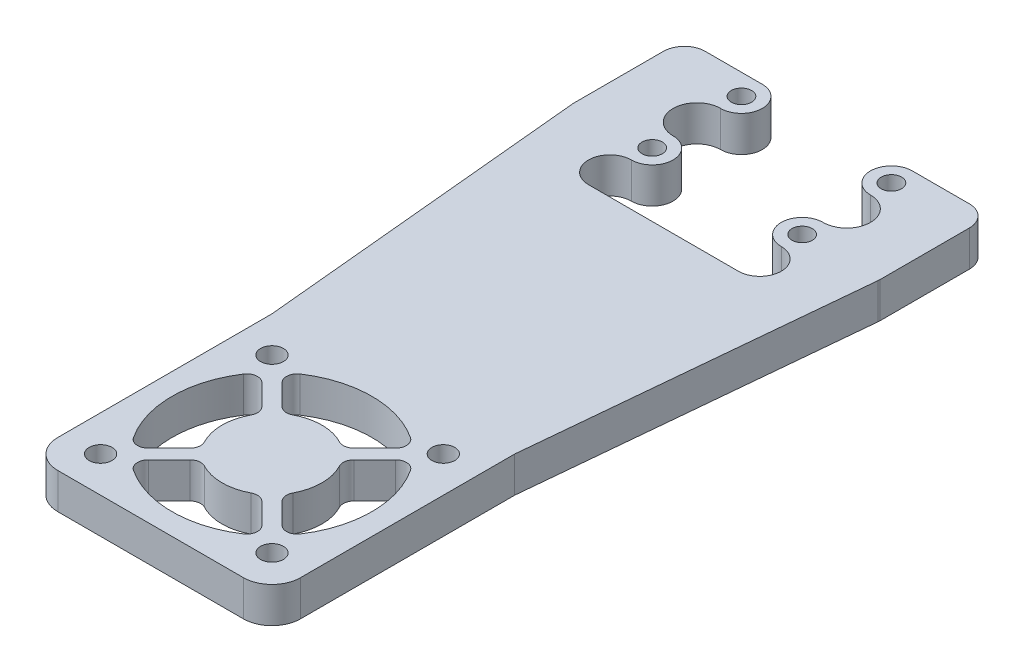
SolidWorks part; units mm, degrees
ref_plane "Front Plane" through (0, 0, 0) normal (0, 0, 1) x (1, 0, 0)
ref_plane "Top Plane" through (0, 0, 0) normal (0, 1, 0) x (1, 0, 0)
ref_plane "Right Plane" through (0, 0, 0) normal (1, 0, 0) x (0, 0, -1)
sketch "Sketch1" plane through (0, 0, 0) normal (0, 1, 0) x (1, 0, 0)
  line L0 (0, 0) -> (0, 70) construction
  line L1 (-12, -12) -> (12, -12) construction
  line L2 (-12, -12) -> (-12, 12) construction
  line L3 (-12, 12) -> (12, 12) construction
  line L4 (12, -12) -> (12, 12) construction
  line L5 (-12, -12) -> (12, 12) construction
  line L6 (-12, 12) -> (12, -12) construction
  line L7 (-17, -17) -> (17, -17)
  line L8 (-17, -17) -> (-17, 17)
  line L9 (-17, 17) -> (17, 17)
  line L10 (17, -17) -> (17, 17)
  line L11 (-17, -17) -> (17, 17) construction
  line L12 (-17, 17) -> (17, -17) construction
  line L13 (10.5, 63.75) -> (18.5, 63.75) construction
  line L14 (-10.5, 76.25) -> (10.5, 76.25) construction
  line L15 (-10.5, 76.25) -> (-10.5, 63.75) construction
  line L16 (-10.5, 63.75) -> (10.5, 63.75) construction
  line L17 (10.5, 76.25) -> (10.5, 63.75) construction
  line L18 (-10.5, 76.25) -> (10.5, 63.75) construction
  line L19 (-10.5, 63.75) -> (10.5, 76.25) construction
  line L20 (10.5, 66.675) -> (18.5, 66.675)
  line L21 (10.5, 60.825) -> (18.5, 60.825)
  line L22 (10.5, 76.25) -> (18.5, 76.25) construction
  line L23 (10.5, 79.175) -> (18.5, 79.175)
  line L24 (10.5, 73.325) -> (18.5, 73.325)
  line L25 (-10.5, 76.25) -> (-18.5, 76.25) construction
  line L26 (-10.5, 73.325) -> (-18.5, 73.325)
  line L27 (-10.5, 79.175) -> (-18.5, 79.175)
  line L28 (-10.5, 63.75) -> (-18.5, 63.75) construction
  line L29 (-10.5, 60.825) -> (-18.5, 60.825)
  line L30 (-10.5, 66.675) -> (-18.5, 66.675)
  line L31 (-17, 17) -> (-17, 60.825)
  line L32 (17, 17) -> (17, 60.825)
  line L33 (-10.5, 54.825) -> (10.5, 54.825)
  line L34 (-21.425, 76.25) -> (-21.425, 63.75)
  line L35 (17, 17) -> (21.4119, 63.4736)
  line L36 (-21.4119, 63.4736) -> (-17, 17)
  line L37 (21.425, 63.75) -> (21.425, 76.25)
  circle A0 centre (-12, 12) radius 1.6
  circle A1 centre (12, 12) radius 1.6
  circle A2 centre (-12, -12) radius 1.6
  circle A3 centre (12, -12) radius 1.6
  circle A4 centre (-10.5, 76.25) radius 1.425
  circle A5 centre (10.5, 76.25) radius 1.425
  circle A6 centre (10.5, 63.75) radius 1.425
  circle A7 centre (-10.5, 63.75) radius 1.425
  arc A8 (10.5, 66.675) -> (10.5, 60.825) centre (10.5, 63.75) ccw
  arc A9 (18.5, 60.825) -> (18.5, 66.675) centre (18.5, 63.75) ccw
  arc A10 (10.5, 79.175) -> (10.5, 73.325) centre (10.5, 76.25) ccw
  arc A11 (18.5, 73.325) -> (18.5, 79.175) centre (18.5, 76.25) ccw
  arc A12 (-10.5, 73.325) -> (-10.5, 79.175) centre (-10.5, 76.25) ccw
  arc A13 (-18.5, 79.175) -> (-18.5, 73.325) centre (-18.5, 76.25) ccw
  arc A14 (-10.5, 60.825) -> (-10.5, 66.675) centre (-10.5, 63.75) ccw
  arc A15 (-18.5, 66.675) -> (-18.5, 60.825) centre (-18.5, 63.75) ccw
  arc A16 (10.5, 60.825) -> (10.5, 54.825) centre (10.5, 57.825) cw
  arc A17 (-10.5, 60.825) -> (-10.5, 54.825) centre (-10.5, 57.825) ccw
  arc A18 (-10.5, 73.325) -> (-10.5, 66.675) centre (-10.5, 70) ccw
  arc A19 (10.5, 66.675) -> (10.5, 73.325) centre (10.5, 70) ccw
  point P0 (0, 0)
  point P10 (0, 0)
  point P25 (14.5, 63.75)
  point P31 (14.5, 76.25)
  point P37 (-14.5, 76.25)
  point P43 (-14.5, 63.75)
  point P65 (22.925, 68.75)
  point P66 (0, 0)
  dimension "D2" = 3.2
  dimension "D7" = 2.85
  dimension "D8" = 2.85
  dimension "D9" = 1.5
  dimension "D11" = 3
  dimension "D1" = 24
  dimension "D3" = 5
  dimension "D4" = 21
  dimension "D5" = 12.5
  dimension "D6" = 70
  dimension "D10" = 8
extrude "Boss-Extrude1" add sketch "Sketch1" along normal blind 5 contours L7 L10 L9 L8 A3 A2 A1 A0 | A17 L29 L31 L9 L32 L21 A16 L33 | A15 L36 L31 L29 | A9 L21 L32 L35 | L21 A9 L20 A8 A6 | A19 L20 A9 L37 A11 L24 | L24 A11 L23 A10 A5 | L27 A13 L26 A12 A4 | A18 L26 A13 L34 A15 L30 | L30 A15 L29 A14 A7 region at (0, 0, 0) region at (0, 0, -36.7282) region at (-18.4223, 0, -46.4573) region at (18.4223, 0, -46.4573) region at (-14.8792, 0, -63.75) region at (14.8792, 0, -63.75) region at (-17.4554, 0, -70) region at (17.4554, 0, -70) region at (-14.8792, 0, -76.25) region at (14.8792, 0, -76.25)
fillet "Fillet1" radius 4 2 edges at (17, 2.5, 17) (-17, 2.5, 17)
sketch "Sketch2" plane through (0, 5, 0) normal (0, 1, 0) x (1, 0, 0)
  line L0 (-12, 12) -> (0, 0) construction
  line L1 (-9.1671, 10.5813) -> (-4.1919, 5.6061)
  line L2 (4.1919, 5.6061) -> (9.1671, 10.5813)
  line L3 (0, 0) -> (12, 12) construction
  line L4 (-6.6795, 8.0937) -> (-7.3866, 7.3866) construction
  line L5 (6.6795, 8.0937) -> (7.3866, 7.3866) construction
  circle A0 centre (0, 0) radius 7
  circle A1 centre (0, 0) radius 14
  dimension "D1" = 14
  dimension "D2" = 28
  dimension "D3" = 1
extrude "Cut-Extrude1" cut sketch "Sketch2" against normal through all both and the other way through all contours L2 A1 L1 A0 region at (0, 5, -10.0852)
fillet "Fillet2" radius 1.5 4 edges
pattern_circular "CirPattern1" count 4 over 360 about axis through (0, 0, 0) along (0, 1, 0) of "Fillet2", "Cut-Extrude1"
